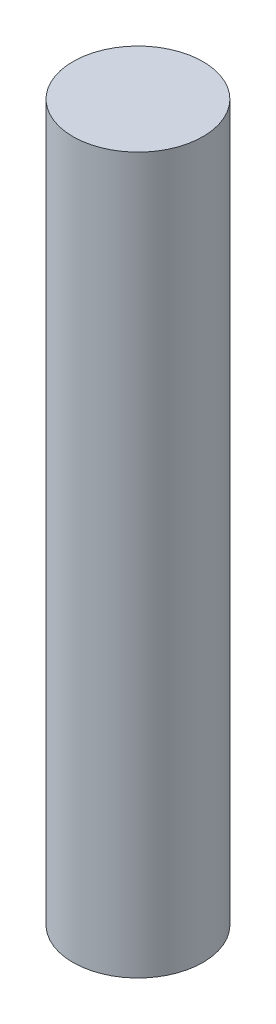
SolidWorks part; units mm, degrees
ref_plane "Front Plane" through (0, 0, 0) normal (0, 0, 1) x (1, 0, 0)
ref_plane "Top Plane" through (0, 0, 0) normal (0, 1, 0) x (1, 0, 0)
ref_plane "Right Plane" through (0, 0, 0) normal (1, 0, 0) x (0, 0, -1)
sketch "Sketch1" plane through (0, 0, 0) normal (0, 1, 0) x (1, 0, 0)
  circle A0 centre (0, 0) radius 1.5
  dimension "D1" = 3
extrude "Boss-Extrude1" add sketch "Sketch1" along normal blind 16.5
ref_plane "Plane1" through (0, 16.5, 0) normal (0, 1, 0) x (1, 0, 0)
ref_point "Point1"
sketch "Sketch2" plane through (0, 16.5, 0) normal (0, 1, 0) x (1, 0, 0)
  circle A0 centre (0, 0) radius 1
  dimension "D1" = 2
ref_plane "Plane2" through (0, 0, 0) normal (0, -1, 0) x (-1, 0, 0)
sketch "Sketch3" plane through (0, 0, 0) normal (0, -1, 0) x (-1, 0, 0)
  line L1 (5.1962, 0) -> (2.5981, 4.5)
  line L2 (2.5981, 4.5) -> (-2.5981, 4.5)
  line L3 (-2.5981, 4.5) -> (-5.1962, 0)
  line L4 (-5.1962, 0) -> (-2.5981, -4.5)
  line L5 (-2.5981, -4.5) -> (2.5981, -4.5)
  line L6 (2.5981, -4.5) -> (5.1962, 0)
  circle A0 centre (0, 0) radius 4.5 construction
sketch "Sketch4" plane through (0, 0, 0) normal (0, -1, 0) x (-1, 0, 0)
  circle A0 centre (0, 0) radius 1.5
  dimension "D1" = 3
ref_plane "Plane3" through (1.5, 0, 0) normal (1, 0, 0) x (0, 0, -1)
sketch "Sketch5" plane through (0, 16.5, 0) normal (0, 1, 0) x (1, 0, 0)
